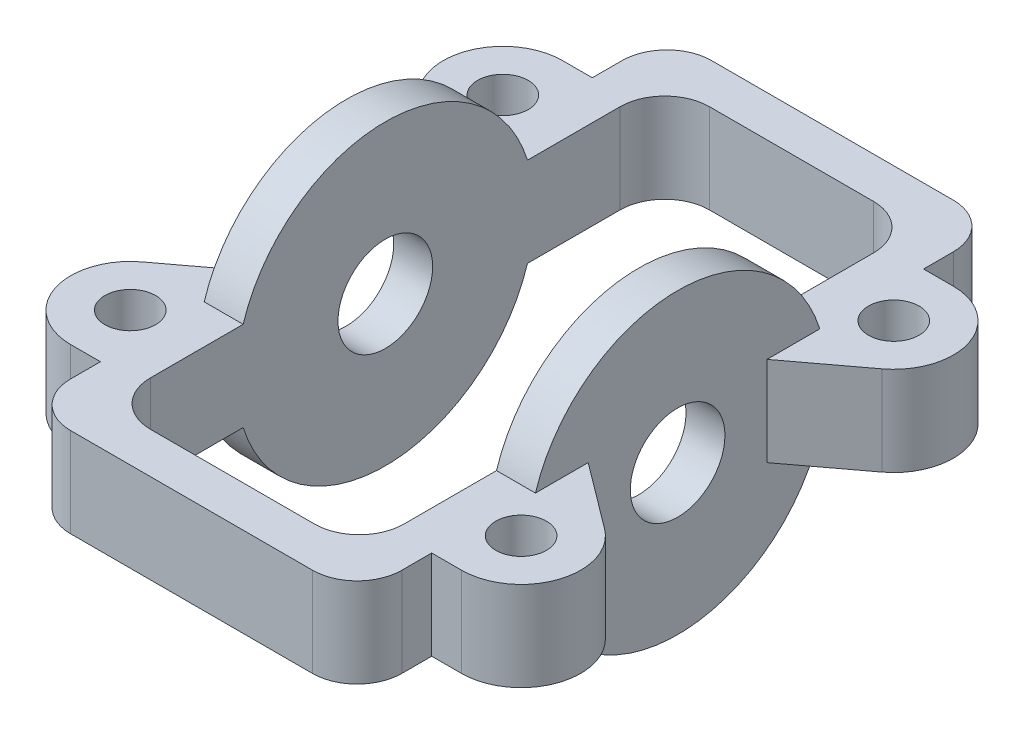
SolidWorks part; units mm, degrees
ref_plane "Front Plane" through (0, 0, 0) normal (0, 0, 1) x (1, 0, 0)
ref_plane "Top Plane" through (0, 0, 0) normal (0, 1, 0) x (1, 0, 0)
ref_plane "Right Plane" through (0, 0, 0) normal (1, 0, 0) x (0, 0, -1)
ref_plane "Ground Plane" through (0, -20.5, 0) normal (0, 1, 0) x (1, 0, 0)
sketch "Sketch1" plane through (0, 0, 0) normal (0, 1, 0) x (1, 0, 0)
  line L0 (7.5, -17.5) -> (7.5, 17.5) construction
  line L1 (-11.1125, -21.5) -> (11.1125, -21.5)
  line L2 (-11.1125, -21.5) -> (-11.1125, 21.5)
  line L3 (-11.1125, 21.5) -> (11.1125, 21.5)
  line L4 (11.1125, -21.5) -> (11.1125, 21.5)
  line L5 (-11.1125, -21.5) -> (11.1125, 21.5) construction
  line L6 (-11.1125, 21.5) -> (11.1125, -21.5) construction
  line L7 (-7.5, 17.5) -> (-7.5, -17.5) construction
  line L8 (7.5, -17.5) -> (7.5, 17.5) construction
  line L9 (-7.5, 17.5) -> (-7.5, -17.5) construction
  point P0 (0, 0)
  dimension "D1" = 22.225
  dimension "D2" = 4
extrude "Boss-Extrude1" add sketch "Sketch1" against normal blind 6
sketch "Sketch3" plane through (11.1125, 0, 0) normal (1, 0, 0) x (0, 0, -1)
  circle A2 centre (0, -3) radius 10
  circle A3 centre (0, -3) radius 17.5 construction
  dimension "D1" = 20
extrude "Boss-Extrude2" add sketch "Sketch3" against normal up to surface (22.225 mm away) up to face at (-11.1125, -3, 0)
sketch "Sketch4" plane through (0, 0, 0) normal (0, 1, 0) x (1, 0, 0)
  line L0 (7.5, -17.5) -> (7.5, 17.5) construction
  line L1 (-7.5, 17.5) -> (-7.5, -17.5) construction
  line L2 (7.5, -17.5) -> (7.5, 17.5) construction
  line L3 (-7.5, 17.5) -> (-7.5, -17.5) construction
  line L4 (-7.5, 17.5) -> (7.5, 17.5) construction
  line L5 (7.5, -17.5) -> (-7.5, -17.5) construction
  line L6 (8.5, -18.75) -> (8.5, 18.75)
  line L7 (-8.5, 18.75) -> (8.5, 18.75)
  line L8 (-8.5, 18.75) -> (-8.5, -18.75)
  line L9 (8.5, -18.75) -> (-8.5, -18.75)
  line L10 (-8.5, 17.5) -> (-7.5, 17.5) construction
  line L11 (-7.5, 17.5) -> (-7.5, 18.75) construction
  line L12 (8.5, -17.5) -> (7.5, -17.5) construction
  line L13 (7.5, -17.5) -> (7.5, -18.75) construction
  dimension "D1" = 1.25
  dimension "D2" = 1
extrude "Cut-Extrude1" cut sketch "Sketch4" against normal through all both and the other way through all
sketch "Sketch5" plane through (0, 0, 0) normal (1, 0, 0) x (0, 0, -1)
  circle A0 centre (0, -3) radius 3.175
  arc A1 (9.5394, 0) -> (-9.5394, 0) centre (0, -3) ccw construction
  dimension "D1" = 6.35
extrude "Cut-Extrude2" cut sketch "Sketch5" against normal through all both and the other way through all
sketch "Sketch7" plane through (0, 0, 0) normal (0, 1, 0) x (1, 0, 0)
  line L0 (11.1125, 16.5) -> (13.1125, 16.5)
  line L1 (13.1125, 8.5) -> (11.1125, 8.5)
  line L2 (11.1125, 9.5394) -> (11.1125, 21.5) construction
  line L3 (11.1125, 8.5) -> (11.1125, 16.5)
  line L4 (11.1125, -16.5) -> (13.1125, -16.5)
  line L5 (13.1125, -8.5) -> (11.1125, -8.5)
  line L6 (11.1125, -21.5) -> (11.1125, -9.5394) construction
  line L7 (11.1125, -8.5) -> (11.1125, -16.5)
  line L8 (0, 0) -> (0, 26.003) construction
  line L9 (-11.1125, -8.5) -> (-11.1125, -16.5)
  line L10 (-13.1125, -8.5) -> (-11.1125, -8.5)
  line L11 (-11.1125, -16.5) -> (-13.1125, -16.5)
  line L12 (-11.1125, 8.5) -> (-11.1125, 16.5)
  line L13 (-13.1125, 8.5) -> (-11.1125, 8.5)
  line L14 (-11.1125, 16.5) -> (-13.1125, 16.5)
  line L15 (13.1125, 8.5) -> (13.1125, -8.5) construction
  line L16 (0, 0) -> (13.1125, 0) construction
  arc A0 (13.1125, 16.5) -> (13.1125, 8.5) centre (13.1125, 12.5) cw
  arc A1 (13.1125, -16.5) -> (13.1125, -8.5) centre (13.1125, -12.5) ccw
  arc A2 (-13.1125, -16.5) -> (-13.1125, -8.5) centre (-13.1125, -12.5) cw
  arc A3 (-13.1125, 16.5) -> (-13.1125, 8.5) centre (-13.1125, 12.5) ccw
  dimension "D1" = 8
  dimension "D2" = 2
  dimension "D3" = 17
extrude "Boss-Extrude3" add sketch "Sketch7" against normal up to surface (6 mm away) up to face at (0, -6, 14.8322)
hole_wizard "M3 Clearance Hole1" positions "Sketch8" profile "Sketch9" hole size "M3" standard "ANSI Metric" end condition through all
sketch "Sketch8" plane through (0, 0, 0) normal (0, 1, 0) x (1, 0, 0)
  point P0 (13.1125, 12.5)
  point P3 (-13.1125, 12.5)
  point P6 (-13.1125, -12.5)
  point P9 (13.1125, -12.5)
sketch "Sketch9" plane through (13.1125, 0, -12.5) normal (1, 0, 0) x (0, 0, 1)
  line L0 (0, 0) -> (0, 13)
  line L1 (0, 13) -> (1.7, 13)
  line L2 (1.7, 13) -> (1.7, 0)
  line L5 (1.7, 0) -> (0, 0)
  line L11 (0, -6.35) -> (0, 107.95) construction
  dimension "Thru Hole Dia." = 3.4
  dimension "Thru Hole Depth" = 13
sketch "Sketch10" plane through (0, 0, 0) normal (0, 1, 0) x (1, 0, 0)
  line L1 (13.1125, -12.5) -> (-13.1125, -12.5)
  line L2 (13.1125, -12.5) -> (13.1125, 12.5)
  line L3 (13.1125, 12.5) -> (-13.1125, 12.5)
  line L4 (-13.1125, -12.5) -> (-13.1125, 12.5)
  line L5 (13.1125, -12.5) -> (-13.1125, 12.5) construction
  line L6 (13.1125, 12.5) -> (-13.1125, -12.5) construction
  point P0 (0, 0)
fillet "Fillet1" radius 3 4 edges at (-11.1125, -3, -21.5) (11.1125, -3, -21.5) (11.1125, -3, 21.5) (-11.1125, -3, 21.5)
fillet "Fillet2" radius 3 4 edges at (8.5, -3, -18.75) (-8.5, -3, -18.75) (-8.5, -3, 18.75) (8.5, -3, 18.75)
sketch "Sketch11" plane through (0, 0, 0) normal (0, 1, 0) x (1, 0, 0)
  line L0 (-15.5125, -9.3) -> (-11.1125, -6)
  line L1 (-11.1125, 9.5394) -> (-11.1125, -9.5394) construction
  line L2 (-11.1125, -6) -> (-11.1125, -8.5)
  line L3 (-11.1125, -8.5) -> (-13.1125, -8.5) construction
  line L4 (-11.1125, -8.5) -> (-13.1125, -8.5)
  line L5 (0, 4.9764) -> (0, 0) construction
  line L6 (0, 0) -> (3.1893, 0) construction
  line L7 (-11.1125, 8.5) -> (-13.1125, 8.5)
  line L8 (-11.1125, 6) -> (-11.1125, 8.5)
  line L9 (-15.5125, 9.3) -> (-11.1125, 6)
  line L10 (15.5125, 9.3) -> (11.1125, 6)
  line L11 (11.1125, 6) -> (11.1125, 8.5)
  line L12 (11.1125, 8.5) -> (13.1125, 8.5)
  line L13 (11.1125, -8.5) -> (13.1125, -8.5)
  line L14 (11.1125, -6) -> (11.1125, -8.5)
  line L15 (15.5125, -9.3) -> (11.1125, -6)
  arc A0 (-13.1125, -8.5) -> (-13.1125, -16.5) centre (-13.1125, -12.5) ccw construction
  arc A1 (-13.1125, -8.5) -> (-15.5125, -9.3) centre (-13.1125, -12.5) ccw
  arc A2 (-13.1125, 8.5) -> (-15.5125, 9.3) centre (-13.1125, 12.5) cw
  arc A3 (13.1125, 8.5) -> (15.5125, 9.3) centre (13.1125, 12.5) ccw
  arc A4 (13.1125, -8.5) -> (15.5125, -9.3) centre (13.1125, -12.5) cw
  dimension "D1" = 2.5
extrude "Boss-Extrude4" add sketch "Sketch11" against normal up to surface (6 mm away) up to face at (13.1125, -6, -14.2)
sketch "Sketch12" plane through (8.5, 0, 0) normal (-1, 0, 0) x (0, 0, 1)
  circle A2 centre (0, -3) radius 3.175 construction
  circle A3 centre (0, -3) radius 3.175
  circle A4 centre (0, -3) radius 7.5
  dimension "D1" = 15
extrude "Boss-Extrude5" [suppressed] add sketch "Sketch12" along normal blind 0.5
mirror "Mirror1" [suppressed] about plane through (0, 0, 0) normal (1, 0, 0)
